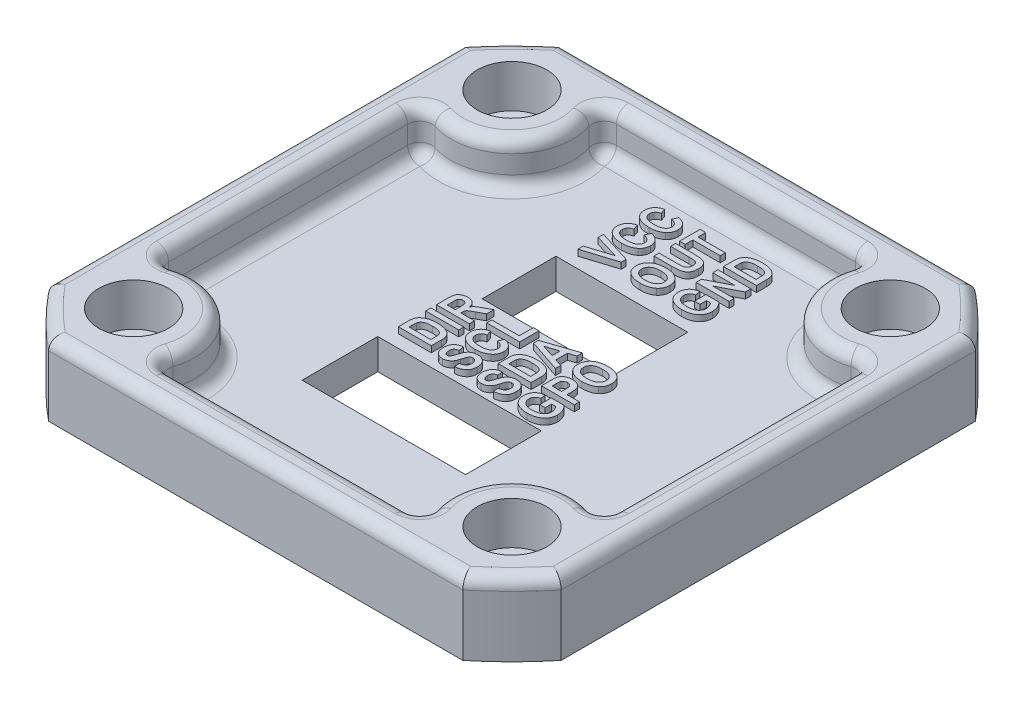
SolidWorks part; units mm, degrees
ref_plane "Front Plane" through (0, 0, 0) normal (0, 0, 1) x (1, 0, 0)
ref_plane "Top Plane" through (0, 0, 0) normal (0, 1, 0) x (1, 0, 0)
ref_plane "Right Plane" through (0, 0, 0) normal (1, 0, 0) x (0, 0, -1)
sketch "Sketch2" plane through (0, 0, 0) normal (0, 1, 0) x (1, 0, 0)
  line L0 (-16.9708, 20.9998) -> (16.9712, 20.9998)
  line L1 (21.0002, 16.9708) -> (21.0002, -16.9712)
  line L2 (16.9712, -21.0002) -> (-16.9708, -21.0002)
  line L3 (-20.9998, 16.9708) -> (-20.9998, -16.9712)
  line L4 (0, 0) -> (0.0002, -0.0002) construction
  line L5 (0.0002, -0.0002) -> (0.0004, -0.0004) construction
  line L6 (0.0004, 0) -> (0.0002, -0.0002) construction
  line L7 (0.0002, -0.0002) -> (0, -0.0004) construction
  line L9 (-11.3916, -18.3502) -> (11.392, -18.3502)
  line L10 (18.3502, -11.392) -> (18.3502, 11.3916)
  line L15 (11.392, 18.3498) -> (-11.3916, 18.3498)
  line L16 (-18.3498, 11.3916) -> (-18.3498, -11.392)
  line L17 (0.0004, 0) -> (0, -0.0004) construction
  line L18 (-5.3998, 8.9998) -> (5.4002, 8.9998)
  line L19 (5.4002, 8.9998) -> (5.4002, 2.9498)
  line L20 (5.4002, 2.9498) -> (-5.3998, 2.9498)
  line L21 (-5.3998, 2.9498) -> (-5.3998, 8.9998)
  line L22 (-6.9998, -4.0002) -> (6.4002, -4.0002)
  line L23 (6.4002, -4.0002) -> (6.4002, -10.2002)
  line L24 (6.4002, -10.2002) -> (-6.9998, -10.2002)
  line L25 (-6.9998, -10.2002) -> (-6.9998, -4.0002)
  arc A0 (16.9712, 20.9998) -> (21.0002, 16.9708) centre (0.0004, 0) cw
  arc A1 (-16.9708, 20.9998) -> (-20.9998, 16.9708) centre (0, 0) ccw
  arc A2 (21.0002, -16.9712) -> (16.9712, -21.0002) centre (0.0004, -0.0004) cw
  arc A3 (-20.9998, -16.9712) -> (-16.9708, -21.0002) centre (0, -0.0004) ccw
  circle A4 centre (-15.4998, 15.4998) radius 1.6
  circle A5 centre (15.5002, 15.4998) radius 1.6
  circle A6 centre (15.5002, -15.5002) radius 1.6
  circle A7 centre (-15.4998, -15.5002) radius 1.6
  circle A8 centre (-15.4998, 15.4998) radius 2.85
  circle A9 centre (15.5002, 15.4998) radius 2.85
  circle A10 centre (-15.4998, -15.5002) radius 2.85
  circle A11 centre (15.5002, -15.5002) radius 2.85
  arc A12 (-18.3498, 11.3916) -> (-11.3916, 18.3498) centre (-15.4998, 15.4998) ccw
  arc A15 (11.392, 18.3498) -> (18.3502, 11.3916) centre (15.5002, 15.4998) ccw
  arc A16 (18.3502, -11.392) -> (11.392, -18.3502) centre (15.5002, -15.5002) ccw
  arc A17 (-11.3916, -18.3502) -> (-18.3498, -11.392) centre (-15.4998, -15.5002) ccw
  point P41 (11.392, -18.3502)
  point P42 (11.392, -18.3502)
  dimension "D4" = 27
  dimension "D7" = 3.2
  dimension "D8" = 5.7
  dimension "D11" = 23.95
  dimension "D12" = 15.6
  dimension "D9" = 5
  dimension "D1" = 42
  dimension "D2" = 42
  dimension "D3" = 33.942
  dimension "D5" = 31
  dimension "D6" = 31
  dimension "D10" = 12
  dimension "D13" = 15.6
  dimension "D14" = 14.6
  dimension "D15" = 14
  dimension "D16" = 10.8
  dimension "D17" = 25
extrude "Boss-Extrude1" add sketch "Sketch2" along normal blind 6 contours L3 A3 L2 A2 L1 A0 L0 A1 A11 A10 A9 A8 L9 A17 L16 A12 L15 A15 L10 A16 region at (0.0002, 0, -20.4058)
extrude "Boss-Extrude2" add sketch "Sketch2<3>" along normal blind 2.5 contours A8 A4 | A9 A5 | A11 A6 | A10 A7 | A17 L9 A16 L10 A15 L15 A12 L16 L24 L25 L22 L23 L20 L21 L18 L19 region at (0.0256, 0, -0.2033) region at (-18.2692, 0, -15.4998) region at (12.7308, 0, -15.4998) region at (-18.2692, 0, 15.5002) region at (12.7308, 0, 15.5002)
sketch "Sketch2<3>" plane through (0, 0, 0) normal (0, 1, 0) x (1, 0, 0) same geometry as "Sketch2"
fillet "Fillet2" radius 1 32 edges at (19.0923, 6, 19.0923) (0.0002, 6, 21.0002) (-19.0919, 6, 19.0923) (-20.9998, 6, 0.0002) (-19.0919, 6, -19.0919) (21.0002, 6, 0.0002) (19.0923, 6, -19.0919) (0.0002, 6, -20.9998) (-11.9643, 6, 11.9647) (-18.3498, 6, 0.0002) (0.0002, 6, 18.3502) (-11.9643, 6, -11.9643) (18.3502, 4.25, 11.392) (11.392, 4.25, 18.3502) (0.0002, 2.5, 18.3502) (-11.9643, 2.5, 11.9647) (-11.3916, 4.25, 18.3502) (-18.3498, 4.25, 11.392) (-18.3498, 4.25, -11.3916) (-11.3916, 4.25, -18.3498) (18.3502, 4.25, -11.3916) (11.392, 4.25, -18.3498) (11.9647, 2.5, 11.9647) (11.9647, 6, 11.9647) (0.0002, 6, -18.3498) (11.9647, 6, -11.9643) (18.3502, 6, 0.0002) (18.3502, 2.5, 0.0002) (11.9647, 2.5, -11.9643) (0.0002, 2.5, -18.3498) (-18.3498, 2.5, 0.0002) (-11.9643, 2.5, -11.9643)
sketch "Sketch3" plane through (0, 2.5, 0) normal (0, 1, 0) x (1, 0, 0)
  line L0 (5.4002, 8.9998) -> (-5.3998, 8.9998) construction
  line L1 (-5.3998, 8.9998) -> (5.4002, 8.9998) construction
  line L2 (5.4002, 8.9998) -> (5.4002, 2.9498) construction
  line L3 (6.4002, -4.0002) -> (-6.9998, -4.0002) construction
  line L4 (-6.9998, -10.2002) -> (6.4002, -10.2002) construction
  line L5 (-1.7998, 8.9998) -> (-1.7998, 17.3498) construction
  line L6 (1.8002, 8.9998) -> (1.8002, 17.3498) construction
  line L7 (-0.2998, -4.0002) -> (-0.2998, 2.9498) construction
  line L8 (-3.6498, -4.0002) -> (-3.6498, 2.9498) construction
  line L9 (3.0502, -4.0002) -> (3.0502, 2.9498) construction
  line L10 (5.4002, 2.9498) -> (-5.3998, 2.9498) construction
  line L11 (9.7925, 17.3498) -> (-9.7921, 17.3498) construction
  line L14 (-6.9998, -4.0002) -> (-6.9998, 2.9498) construction
  line L15 (-6.9998, 2.9498) -> (-3.6498, 2.9498) construction
  line L16 (-3.6498, 2.9498) -> (-0.2998, 2.9498) construction
  line L17 (-0.2998, 2.9498) -> (3.0502, 2.9498) construction
  line L18 (3.0502, 2.9498) -> (6.4002, 2.9498) construction
  line L19 (6.4002, 2.9498) -> (6.4002, -4.0002) construction
  line L20 (-5.3998, 8.9998) -> (-5.3998, 17.3498) construction
  line L21 (-5.3998, 17.3498) -> (-1.7998, 17.3498) construction
  line L22 (-1.7998, 17.3498) -> (1.8002, 17.3498) construction
  line L23 (1.8002, 17.3498) -> (5.4002, 17.3498) construction
  line L24 (5.4002, 17.3498) -> (5.4002, 8.9998) construction
  text T0 "<b>DIR</b>"
  text T1 "SCL\r\n"
  text T2 "SDA\r\n"
  text T3 "GPO"
  text T4 "VCC"
  text T5 "OUT"
  text T6 "GND"
extrude "Boss-Extrude3" add sketch "Sketch3" along normal blind 0.5
